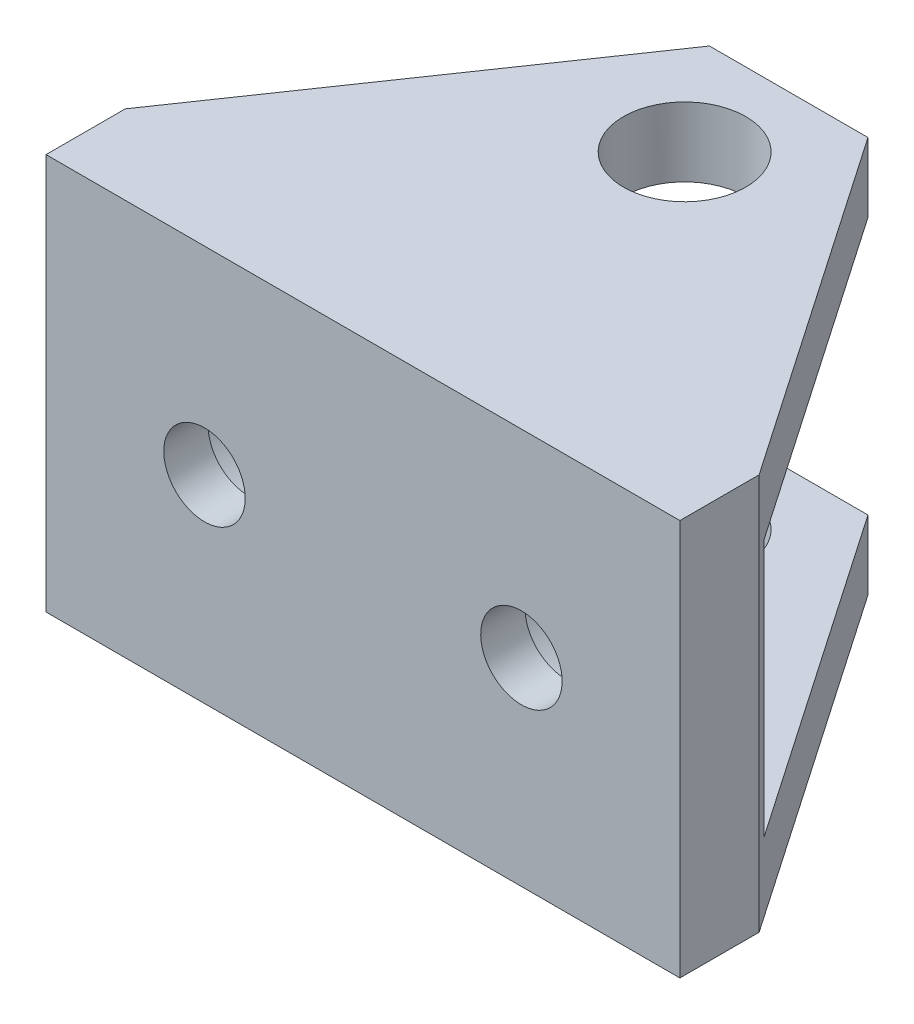
SolidWorks part; units mm, degrees
material "6061-T6 (SS)"
ref_plane "X-Y Datum" through (0, 0, 0) normal (0, 0, 1) x (1, 0, 0)
ref_plane "X-Z Datum" through (0, 0, 0) normal (0, 1, 0) x (1, 0, 0)
ref_plane "Y-Z Datum" through (0, 0, 0) normal (1, 0, 0) x (0, 0, -1)
sketch "Sketch1" plane through (0, 0, 0) normal (1, 0, 0) x (0, 0, -1)
  line L0 (0, 0) -> (0, 31.75)
  line L1 (0, 31.75) -> (38.4801, 31.75)
  line L2 (38.4801, 31.75) -> (38.4801, 26.2001)
  line L3 (38.4801, 26.2001) -> (7.62, 26.2001)
  line L4 (7.62, 26.2001) -> (7.62, 5.5499)
  line L5 (7.62, 5.5499) -> (38.4801, 5.5499)
  line L6 (38.4801, 5.5499) -> (38.4801, 0)
  line L7 (38.4801, 0) -> (0, 0)
  line L8 (25.7801, 31.75) -> (25.7801, 0) construction
  dimension "D1" = 20.6502
  dimension "D2" = 31.75
  dimension "D3" = 12.7
  dimension "D4" = 7.62
extrude "Boss-Extrude1" add sketch "Sketch1" along normal blind 50.8
sketch "Sketch2" plane through (0, 0, -7.62) normal (0, 0, -1) x (-1, 0, 0)
  line L0 (-50.8, 15.875) -> (0, 15.875) construction
  line L1 (-50.8, 5.5499) -> (-50.8, 26.2001) construction
  line L2 (0, 5.5499) -> (0, 26.2001) construction
  line L3 (-25.4, 5.5499) -> (-25.4, 26.2001) construction
  line L4 (-50.8, 5.5499) -> (0, 5.5499) construction
  line L5 (-50.8, 26.2001) -> (0, 26.2001) construction
  point P6 (-38.1, 15.875)
  point P7 (-12.7, 15.875)
  dimension "D1" = 25.4
  dimension "D2" = 12.7
hole_wizard "CBORE for 1/4 Binding Head Machine Screw1" positions "Sketch2" profile "Sketch3" counterbore size "1/4" standard "ANSI Inch" end condition through all
sketch "Sketch3" plane through (12.7, 15.875, -7.62) normal (1, 0, 0) x (0, 1, 0)
  line L0 (0, 0) -> (0, 7.62)
  line L1 (0, 7.62) -> (3.2639, 7.62)
  line L3 (3.2639, 7.62) -> (3.2639, 4.064)
  line L4 (3.2639, 4.064) -> (7.1437, 4.064)
  line L5 (7.1437, 4.064) -> (7.1438, 0)
  line L7 (7.1438, 0) -> (0, 0)
  line L11 (0, -6.35) -> (0, 107.95) construction
  dimension "Thru Hole Dia." = 6.5278
  dimension "Thru Hole Depth" = 7.62
  dimension "C'Bore Dia." = 14.2875
  dimension "C'Bore Depth" = 4.064
sketch "Sketch4" plane through (0, 0, 0) normal (0, -1, 0) x (1, 0, 0)
  line L0 (25.4, 0) -> (25.4, -38.4801) construction
  line L1 (50.8, 0) -> (0, 0) construction
  line L2 (50.8, -38.4801) -> (0, -38.4801) construction
  line L3 (19.05, -34.124) -> (0, -6.35)
  line L4 (31.75, -34.124) -> (50.8, -6.35)
  line L5 (0, -6.35) -> (0, -38.4801)
  line L6 (0, -38.4801) -> (50.8, -38.4801)
  line L7 (50.8, -38.4801) -> (50.8, -6.35)
  line L8 (0, 0) -> (0, -38.4801) construction
  line L9 (50.8, 0) -> (50.8, -38.4801) construction
  line L10 (19.05, -34.124) -> (31.75, -34.124)
  circle A0 centre (25.4, -25.7801) radius 4.9022
  dimension "D1" = 9.8044
  dimension "D2" = 6.35
  dimension "D3" = 8.3439
  dimension "D4" = 12.7
extrude "Cut-Extrude1" cut sketch "Sketch4" against normal up to surface (31.75 mm away) up to face at (25.4, 31.75, -19.2401)
